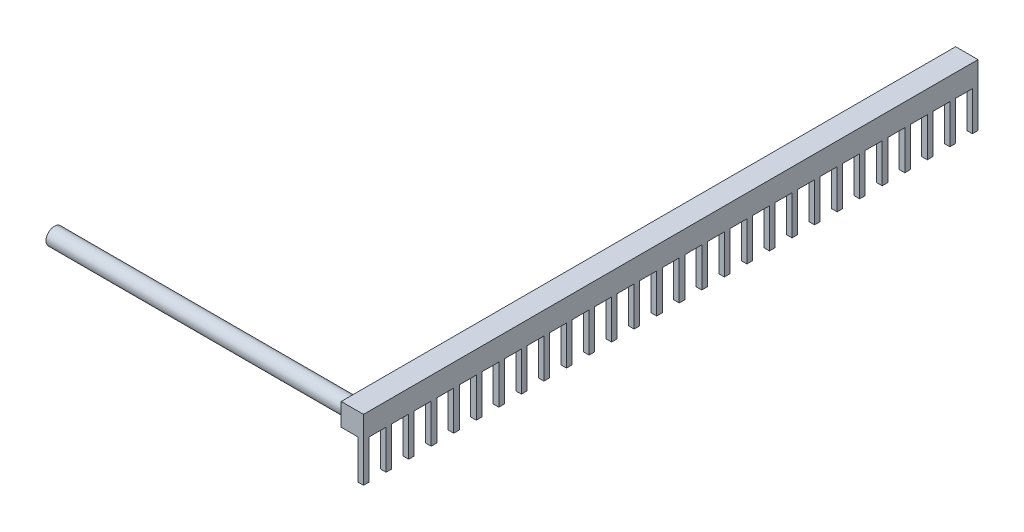
SolidWorks part; units mm, degrees
ref_plane "Front Plane" through (0, 0, 0) normal (0, 0, 1) x (1, 0, 0)
ref_plane "Top Plane" through (0, 0, 0) normal (0, 1, 0) x (1, 0, 0)
ref_plane "Right Plane" through (0, 0, 0) normal (1, 0, 0) x (0, 0, -1)
sketch "Sketch1" plane through (0, 0, 0) normal (0, 0, 1) x (1, 0, 0)
  line L1 (0, 0) -> (-20, 0)
  line L2 (0, 0) -> (0, 20)
  line L3 (0, 20) -> (-20, 20)
  line L4 (-20, 0) -> (-20, 20)
  dimension "D1" = 20
extrude "Boss-Extrude1" add sketch "Sketch1" along normal blind 550
sketch "Sketch2" plane through (-20, 0, 0) normal (-1, 0, 0) x (0, 0, 1)
  line L0 (550, 20) -> (0, 20) construction
  line L1 (550, 0) -> (530, 0)
  line L2 (550, 0) -> (550, 20)
  line L3 (550, 20) -> (530, 20)
  line L4 (530, 0) -> (530, 20)
  line L5 (530, 20) -> (550, 0)
  circle A0 centre (540, 10) radius 7.5
  dimension "D1" = 15
extrude "Boss-Extrude2" add sketch "Sketch2" along normal blind 266.7 contours A0
sketch "Sketch3" plane through (0, 0, 550) normal (0, 0, 1) x (1, 0, 0)
  line L1 (0, 0) -> (-5, 0)
  line L2 (0, 0) -> (0, -35)
  line L3 (0, -35) -> (-5, -35)
  line L4 (-5, 0) -> (-5, -35)
  dimension "D1" = 5
  dimension "D2" = 35
extrude "Boss-Extrude3" add sketch "Sketch3" against normal blind 5
pattern_linear "LPattern1" count 28 spacing 20.1852 along (0, 0, -1) of "Boss-Extrude3"
